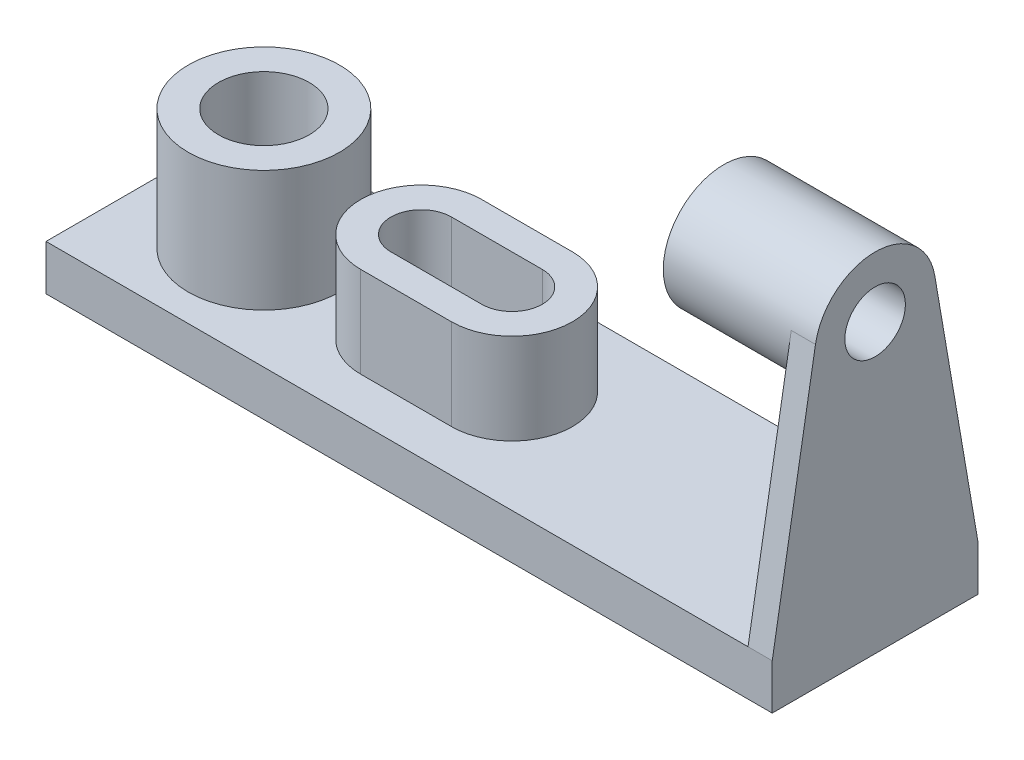
SolidWorks part; units mm, degrees
ref_plane "Front Plane" through (0, 0, 0) normal (0, 0, 1) x (1, 0, 0)
ref_plane "Top Plane" through (0, 0, 0) normal (0, 1, 0) x (1, 0, 0)
ref_plane "Right Plane" through (0, 0, 0) normal (1, 0, 0) x (0, 0, -1)
sketch "Sketch2" plane through (0, 0, 0) normal (0, 1, 0) x (1, 0, 0)
  line L0 (-82, 0) -> (-120, 0) construction
  line L1 (-120, 34) -> (120, 34)
  line L2 (-120, 34) -> (-120, -34)
  line L3 (-120, -34) -> (120, -34)
  line L4 (120, 34) -> (120, -34)
  line L5 (-120, 34) -> (120, -34) construction
  line L6 (-120, -34) -> (120, 34) construction
  circle A0 centre (-82, 0) radius 25
  circle A1 centre (-82, 0) radius 15
  point P0 (0, 0)
  dimension "D1" = 50
  dimension "D4" = 30
  dimension "D2" = 68
  dimension "D3" = 240
  dimension "D5" = 202
extrude "Boss-Extrude1" add sketch "Sketch2" against normal blind 15 contours L4 L1 L2 L3 A0 region at (11.2149, 0, 0)
extrude "Boss-Extrude3" add sketch "Sketch2<4>" along normal blind 40 separate body contours A0
sketch "Sketch2<4>" plane through (0, 0, 0) normal (0, 1, 0) x (1, 0, 0) same geometry as "Sketch2"
extrude "Cut-Extrude1" cut sketch "Sketch2<5>" along normal blind 52 contours A1
sketch "Sketch2<5>" plane through (0, 0, 0) normal (0, 1, 0) x (1, 0, 0) same geometry as "Sketch2"
sketch "Sketch4" plane through (0, 0, 0) normal (0, 1, 0) x (1, 0, 0)
  line L0 (-82, 0) -> (120, 0) construction
  line L1 (120, 34) -> (120, -34) construction
  line L2 (-30, 0) -> (0, 0) construction
  line L3 (-30, 20) -> (0, 20)
  line L4 (-30, -20) -> (0, -20)
  line L5 (-30, 10) -> (0, 10)
  line L6 (-30, -10) -> (0, -10)
  arc A0 (-30, 20) -> (-30, -20) centre (-30, 0) ccw
  arc A1 (0, -20) -> (0, 20) centre (0, 0) ccw
  arc A2 (0, -10) -> (0, 10) centre (0, 0) ccw
  arc A3 (-30, 10) -> (-30, -10) centre (-30, 0) ccw
  point P8 (-15, 0)
  dimension "D1" = 20
  dimension "D2" = 30
  dimension "D3" = 135
  dimension "D4" = 10
extrude "Boss-Extrude6" add sketch "Sketch4" along normal blind 30
sketch "Sketch6" plane through (0, 0, 0) normal (0, 1, 0) x (1, 0, 0)
  line L2 (-30, -10) -> (0, -10)
  line L3 (0, 10) -> (-30, 10)
  line L4 (-30, -10) -> (0, -10)
  line L5 (0, 10) -> (-30, 10)
  arc A2 (-30, 10) -> (-30, -10) centre (-30, 0) ccw
  arc A3 (0, -10) -> (0, 10) centre (0, 0) ccw
  arc A4 (-30, 10) -> (-30, -10) centre (-30, 0) ccw
  arc A5 (0, -10) -> (0, 10) centre (0, 0) ccw
  dimension "D1" = 0
extrude "Cut-Extrude3" cut sketch "Sketch6" against normal blind 30 and the other way blind 30
sketch "Sketch8" plane through (0, 0, 0) normal (0, 0, 1) x (1, 0, 0)
  line L0 (-57, 20) -> (-50, 20)
  line L4 (-57, 0) -> (-57, 40) construction
  line L5 (-50, 30) -> (-50, 0) construction
  dimension "D1" = 20
sketch "Sketch9" plane through (120, 0, 0) normal (1, 0, 0) x (0, 0, -1)
  line L0 (0, 0) -> (0, 75.7033) construction
  line L1 (0, 75.7033) -> (0, 80) construction
  line L2 (-34, 0) -> (-19.7127, 83.3779)
  line L6 (19.7378, 83.2278) -> (34, 0)
  line L7 (-34, 0) -> (34, 0)
  line L8 (34, -15) -> (-34, -15) construction
  arc A0 (19.7378, 83.2278) -> (-19.7127, 83.3779) centre (0, 80) ccw
  circle A1 centre (0, 80) radius 10
  dimension "D1" = 20
  dimension "D3" = 20
  dimension "D2" = 95
extrude "Boss-Extrude7" add sketch "Sketch9" against normal blind 8
sketch "Sketch10" plane through (112, 0, 0) normal (-1, 0, 0) x (0, 0, 1)
  circle A0 centre (0, 80) radius 20
  circle A1 centre (0, 80) radius 10
extrude "Boss-Extrude8" add sketch "Sketch10" along normal blind 42
sketch "Sketch11" plane through (0, 0, 0) normal (0, 0, 1) x (1, 0, 0)
  line L0 (81.641, 60) -> (47, 0)
  line L1 (70, 60) -> (112, 60) construction
  line L2 (-120, 0) -> (120, 0) construction
  line L3 (-120, 0) -> (120, 0) construction
  line L4 (47, 0) -> (112, 0)
  line L5 (112, 0) -> (112, 60)
  line L6 (112, 83.3779) -> (112, 0) construction
  line L7 (112, 60) -> (81.641, 60)
  dimension "D1" = 65
  dimension "D2" = 60
